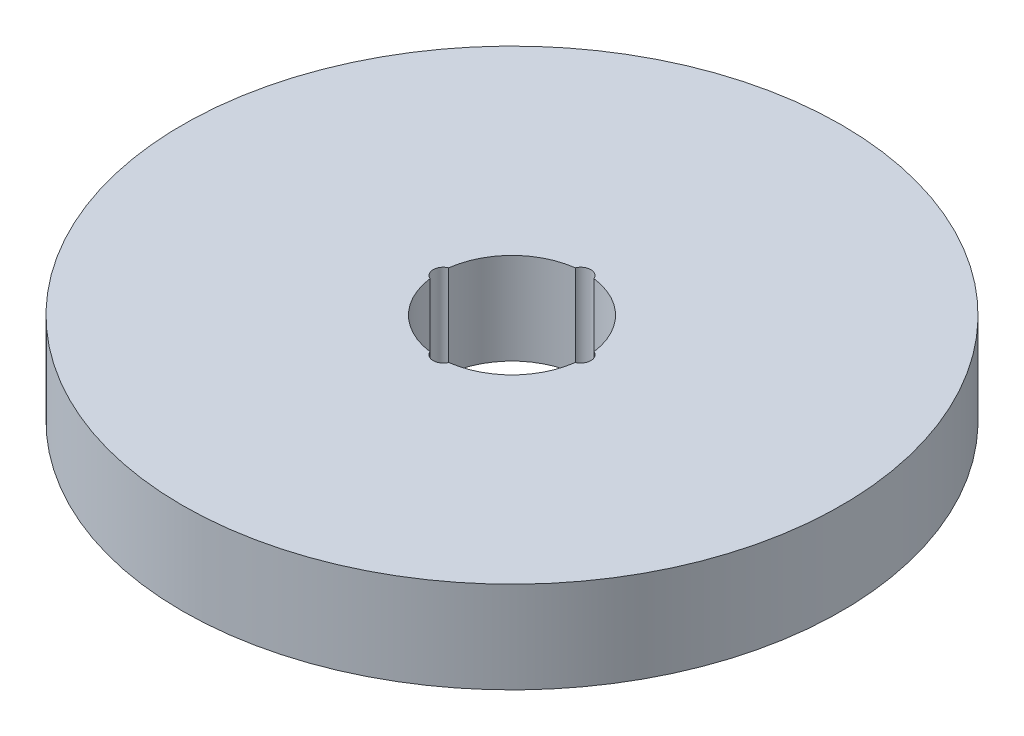
SolidWorks part; units mm, degrees
ref_plane "Front Plane" through (0, 0, 0) normal (0, 0, 1) x (1, 0, 0)
ref_plane "Top Plane" through (0, 0, 0) normal (0, 1, 0) x (1, 0, 0)
ref_plane "Right Plane" through (0, 0, 0) normal (1, 0, 0) x (0, 0, -1)
sketch "Sketch1" plane through (0, 0, 0) normal (0, 1, 0) x (1, 0, 0)
  circle A0 centre (0, 0) radius 90
  dimension "FLANGE_OD" = 180
extrude "Boss-Extrude1" add sketch "Sketch1" along normal blind 25
sketch "Sketch2" plane through (0, 0, 0) normal (0, 1, 0) x (1, 0, 0)
  circle A0 centre (0, 0) radius 20
  dimension "BORE_D" = 40
extrude "Cut-Extrude1" cut sketch "Sketch2" along normal through all
sketch "Sketch3" plane through (0, 25, 0) normal (0, 1, 0) x (1, 0, 0)
  circle A0 centre (0, 0) radius 18.758 construction
  circle A1 centre (-18.758, 0) radius 2.7756
  dimension "BOLT_D" = 5.5512
  dimension "BOLT_PCD" = 37.5161
extrude "Cut-Extrude2" cut sketch "Sketch3" against normal blind 24.8367
pattern_circular "CirPattern1" count 4 over 360 about axis through (0, 0, 0) along (0, 1, 0) of "Cut-Extrude2"
